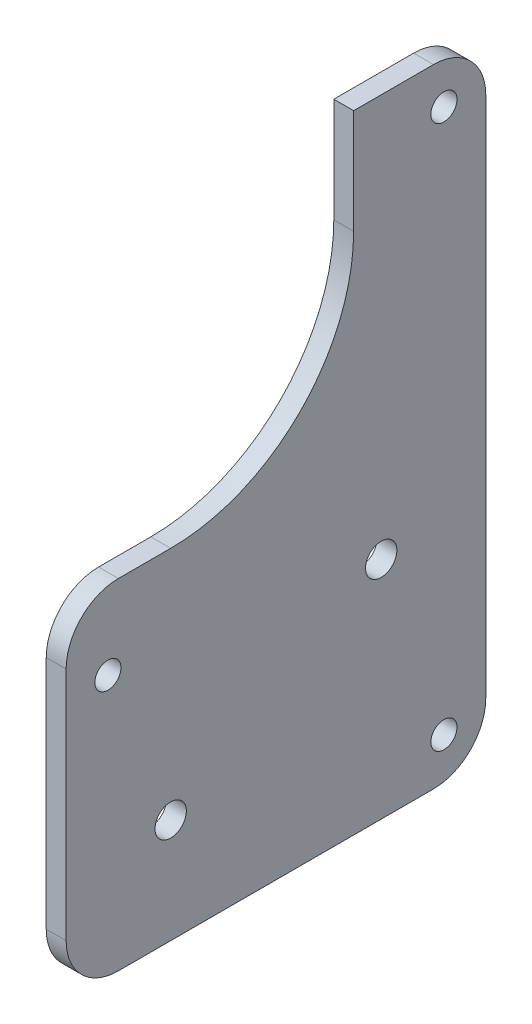
SolidWorks part; units mm, degrees
ref_plane "Front Plane" through (0, 0, 0) normal (0, 0, 1) x (1, 0, 0)
ref_plane "Top Plane" through (0, 0, 0) normal (0, 1, 0) x (1, 0, 0)
ref_plane "Right Plane" through (0, 0, 0) normal (1, 0, 0) x (0, 0, -1)
sketch "Sketch1" plane through (0, 0, 0) normal (1, 0, 0) x (0, 0, -1)
  line L0 (-13.7601, 29.375) -> (-13.7601, -50.625) construction
  line L1 (-13.7601, -27.5756) -> (26.5101, -27.5756) construction
  line L2 (-33.7601, 49.375) -> (46.5101, 49.375) construction
  line L3 (-33.7601, 49.375) -> (-33.7601, -70.625) construction
  line L4 (-33.7601, -70.625) -> (46.5101, -70.625)
  line L5 (46.5101, 49.375) -> (46.5101, -70.625)
  line L6 (21.2399, 29.375) -> (21.2399, 49.375)
  line L7 (-13.7601, -5.625) -> (-33.7601, -5.625)
  line L8 (-33.7601, -5.625) -> (-33.7601, -70.625)
  line L9 (21.2399, 49.375) -> (46.5101, 49.375)
  line L10 (38.5101, 49.375) -> (38.5101, 41.375) construction
  line L11 (38.5101, 41.375) -> (46.5101, 41.375) construction
  line L12 (46.5101, -10.625) -> (-33.7601, -10.625) construction
  line L13 (-33.7601, -20.625) -> (-25.7601, -20.625) construction
  circle A0 centre (-13.7601, 29.375) radius 4 construction
  circle A1 centre (-13.7601, -50.625) radius 3
  circle A2 centre (26.5101, -27.5756) radius 3
  circle A3 centre (-13.7601, -50.625) radius 17.9 construction
  circle A4 centre (-13.7601, 29.375) radius 41.25 construction
  circle A5 centre (26.5101, -27.5756) radius 28.5 construction
  arc A6 (-13.7601, -5.625) -> (21.2399, 29.375) centre (-13.7601, 29.375) ccw
  circle A7 centre (38.5101, 41.375) radius 2.5
  circle A8 centre (38.5101, -62.625) radius 2.5
  circle A10 centre (-25.7601, -20.625) radius 2.5
  point P23 (-13.7601, -50.625)
  dimension "D1" = 8
  dimension "D2" = 6
  dimension "D3" = 6
  dimension "D4" = 82.5
  dimension "D5" = 35.8
  dimension "D6" = 57
  dimension "D12" = 10
  dimension "D7" = 80
  dimension "D8" = 20
  dimension "D9" = 20
  dimension "D10" = 20
  dimension "D11" = 20
extrude "Boss-Extrude1" add sketch "Sketch1" along normal blind 3.8
fillet "Fillet1" radius 10 4 edges at (1.9, -70.625, -46.5101) (1.9, 49.375, -46.5101) (1.9, -5.625, 33.7601) (1.9, -70.625, 33.7601)
